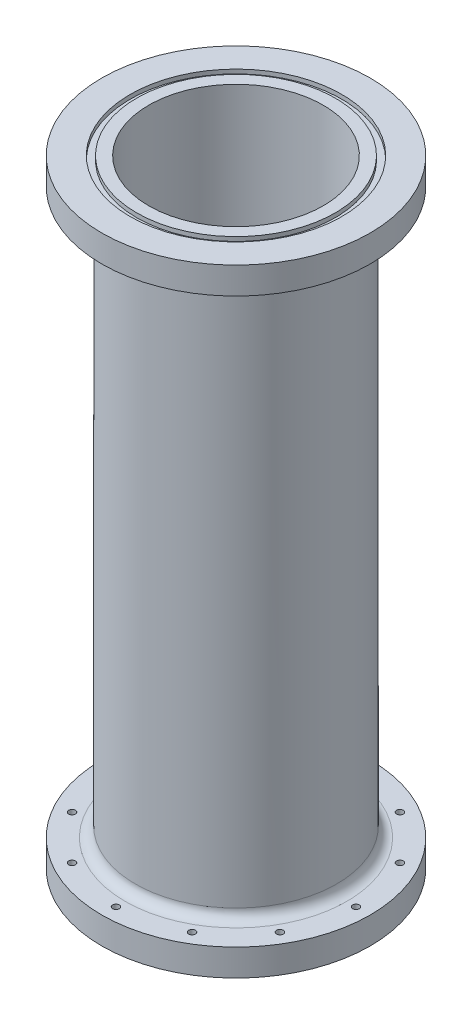
SolidWorks part; units mm, degrees
ref_plane "Front Plane" through (0, 0, 0) normal (0, 0, 1) x (1, 0, 0)
ref_plane "Top Plane" through (0, 0, 0) normal (0, 1, 0) x (1, 0, 0)
ref_plane "Right Plane" through (0, 0, 0) normal (1, 0, 0) x (0, 0, -1)
sketch "Sketch2" plane through (0, 0, 0) normal (0, 1, 0) x (1, 0, 0)
  circle A0 centre (0, 0) radius 41.275
  circle A1 centre (0, 0) radius 47.625
  dimension "D1" = 95.25
  dimension "D2" = 82.55
extrude "Base Cylinder" add sketch "Sketch2" along normal blind 292.1
sketch "Sketch3" plane through (0, 0, 0) normal (0, -1, 0) x (1, 0, 0)
  circle A0 centre (0, 0) radius 41.275
  circle A1 centre (0, 0) radius 63.5
  dimension "D1" = 127
extrude "Aft Flange" add sketch "Sketch3" against normal blind 12.7
sketch "Sketch4" plane through (0, 292.1, 0) normal (0, 1, 0) x (1, 0, 0)
  circle A0 centre (0, 0) radius 41.275
  circle A1 centre (0, 0) radius 63.5
  dimension "D1" = 127
extrude "Forward Flange" add sketch "Sketch4" against normal blind 12.7
sketch "Sketch6" plane through (0, 0, 0) normal (0, -1, 0) x (1, 0, 0)
  circle A0 centre (0, 0) radius 50.0761
  circle A1 centre (0, 0) radius 47.0027
  dimension "D1" = 100.1522
  dimension "D2" = 94.0054
extrude "Aft O-Ring" cut sketch "Sketch6" against normal blind 1.9812
sketch "Sketch7" plane through (0, 292.1, 0) normal (0, 1, 0) x (1, 0, 0)
  circle A0 centre (0, 0) radius 50.0761
  circle A1 centre (0, 0) radius 47.0027
  dimension "D1" = 100.1522
  dimension "D2" = 94.0054
extrude "Forward O-Ring" cut sketch "Sketch7" against normal blind 1.9812
sketch "Sketch For Bolt Holes" plane through (0, 0, 0) normal (0, -1, 0) x (1, 0, 0)
  circle A0 centre (-56.769, 0) radius 1.5875
  circle A1 centre (-49.1634, 28.3845) radius 1.5875
  circle A2 centre (-28.3845, 49.1634) radius 1.5875
  circle A3 centre (0, 56.769) radius 1.5875
  circle A4 centre (28.3845, 49.1634) radius 1.5875
  circle A5 centre (49.1634, 28.3845) radius 1.5875
  circle A6 centre (56.769, 0) radius 1.5875
  circle A7 centre (49.1634, -28.3845) radius 1.5875
  circle A8 centre (28.3845, -49.1634) radius 1.5875
  circle A9 centre (0, -56.769) radius 1.5875
  circle A10 centre (-28.3845, -49.1634) radius 1.5875
  circle A11 centre (-49.1634, -28.3845) radius 1.5875
  point P36 (0, 0)
  dimension "D2" = 3.175
  dimension "D1" = 56.769
  dimension "D3" = 12
hole_wizard "1/8 (0.125) Diameter Hole2" positions "Sketch8" profile "Sketch9" hole size "1/8" standard "ANSI Inch"
sketch "Sketch8" plane through (0, 0, 0) normal (0, -1, 0) x (-1, 0, 0)
  point P0 (-28.3845, -49.1634)
  point P3 (-49.1634, -28.3845)
  point P6 (-56.769, 0)
  point P9 (-49.1634, 28.3845)
  point P12 (-28.3845, 49.1634)
  point P15 (0, 56.769)
  point P18 (28.3845, 49.1634)
  point P21 (49.1634, 28.3845)
  point P24 (56.769, 0)
  point P27 (49.1634, -28.3845)
  point P30 (28.3845, -49.1634)
  point P33 (0, -56.769)
  point P36 (-28.3845, -49.1634)
  point P38 (-49.1634, -28.3845)
  point P40 (-56.769, 0)
sketch "Sketch9" plane through (28.3845, 0, 49.1634) normal (1, 0, 0) x (0, 0, -1)
  line L0 (0, 0) -> (0, 26.3539)
  line L1 (0, 26.3539) -> (1.5875, 25.4)
  line L2 (1.5875, 25.4) -> (1.5875, 0)
  line L5 (1.5875, 0) -> (0, 0)
  line L10 (0, 26.3539) -> (-1.5875, 25.4) construction
  line L11 (0, -6.35) -> (0, 107.95) construction
  dimension "Hole Dia." = 3.175
  dimension "Hole Depth" = 25.4
  dimension "Drill Angle" = 118
fillet "Flange Fillet" radius 4.7625 2 edges at (0, 12.7, -47.625) (0, 279.4, 47.625)
